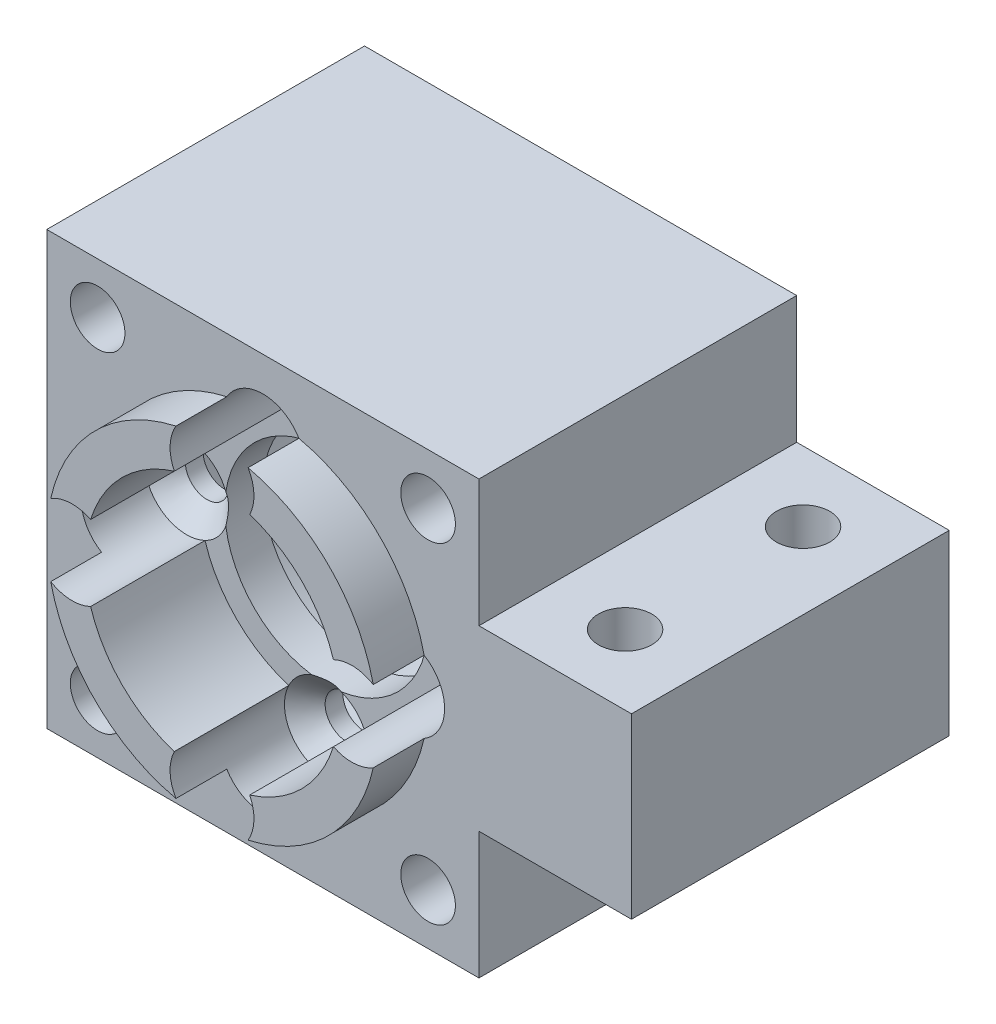
SolidWorks part; units mm, degrees
material "1060 合金"
ref_plane "前视基准面" through (0, 0, 0) normal (0, 0, 1) x (1, 0, 0)
ref_plane "上视基准面" through (0, 0, 0) normal (0, 1, 0) x (1, 0, 0)
ref_plane "右视基准面" through (0, 0, 0) normal (1, 0, 0) x (0, 0, -1)
sketch "草图1" plane through (0, 0, 0) normal (1, 0, 0) x (0, 0, -1)
  line L0 (0, 0) -> (85.2801, 0) construction
  line L1 (0, 0) -> (0, 40.8583) construction
  line L2 (0, 13) -> (0, 10)
  line L3 (0, 10) -> (9, 10)
  line L4 (9, 10) -> (9, 8)
  line L5 (9, 8) -> (12, 8)
  line L6 (12, 8) -> (12, 14)
  line L7 (12, 14) -> (29, 14)
  line L8 (29, 14) -> (29, 16)
  line L9 (29, 16) -> (4, 16)
  line L10 (0, 13) -> (4, 13)
  line L11 (4, 13) -> (4, 16)
  dimension "D1" = 8
  dimension "D2" = 3
  dimension "D3" = 13
  dimension "D4" = 14
  dimension "D5" = 2
  dimension "D6" = 17
  dimension "D7" = 4
  dimension "D8" = 8
  dimension "D9" = 10
revolve "旋转1" add sketch "草图1" angle 360 about L0
hole_wizard "打孔尺寸(%根据十字)槽沉头木螺钉的类型1" positions "草图3" profile "草图2" countersink size "M3" standard "GB" end condition through all
sketch "草图3" plane through (0, 0, 0) normal (0, 0, 1) x (1, 0, 0)
  line L0 (11, 0) -> (0, 0) construction
  line L2 (0, 0) -> (4.7674, 0) construction
  line L3 (0, 0) -> (0, 6.1766) construction
  circle A0 centre (0, 0) radius 11 construction
  point P0 (11, 0)
  point P12 (0, -11)
  point P13 (-11, 0)
  point P14 (0, 11)
  dimension "D1" = 22
  dimension "D2" = 4
sketch "草图2" plane through (11, 0, 0) normal (1, 0, 0) x (0, -1, 0)
  line L0 (0, 0) -> (0, 29)
  line L1 (0, 29) -> (1.7, 29)
  line L2 (1.7, 29) -> (1.7, 10.6)
  line L3 (1.7, 10.6) -> (3.3, 9)
  line L4 (3.3, 9) -> (3.3, 0)
  line L6 (3.3, 0) -> (0, 0)
  line L7 (-1.7, 10.6) -> (-3.3, 9) construction
  line L11 (0, -6.35) -> (0, 107.95) construction
  dimension "通孔孔直径" = 3.4
  dimension "通孔孔深度" = 29
  dimension "锥形沉头孔直径" = 6.6
  dimension "锥形沉头孔角度" = 90
  dimension "头间隙" = 9
sketch "草图4" plane through (0, 0, -4) normal (0, 0, 1) x (1, 0, 0)
  line L1 (-17, -17) -> (17, -17)
  line L2 (-17, -17) -> (-17, 17)
  line L3 (-17, 17) -> (17, 17)
  line L4 (17, -17) -> (17, 17)
  line L5 (-17, -17) -> (17, 17) construction
  line L6 (-17, 17) -> (17, -17) construction
  circle A0 centre (0, 0) radius 16
  circle A1 centre (0, 0) radius 16 construction
  point P0 (0, 0)
  dimension "D1" = 34
extrude "凸台-拉伸1" add sketch "草图4" against normal up to surface (25 mm away) up to face at (16, 0, -29)
sketch "草图11" [suppressed] plane through (0, 0, -29) normal (0, 0, -1) x (-1, 0, 0)
  line L0 (0, 0) -> (0, 25.5096) construction
  line L3 (-17, 17) -> (17, 17) construction
  line L4 (-10, 9.798) -> (10, 9.798) construction
  line L5 (-10, 9.798) -> (-10, 17)
  line L6 (-10, 17) -> (10, 17)
  line L7 (10, 9.798) -> (10, 17)
  line L8 (-10, 9.798) -> (10, 17) construction
  line L9 (-10, 17) -> (10, 9.798) construction
  circle A4 centre (0, 0) radius 14 construction
  circle A5 centre (0, 0) radius 14 construction
  arc A6 (10, 9.798) -> (-10, 9.798) centre (0, 0) ccw
  point P3 (0, 13.399)
  dimension "D1" = 20
extrude "凸台-拉伸2" [suppressed] add sketch "草图11" along normal up to surface (21 mm away) up to face at (14, 0, -29)
hole_wizard "打孔尺寸(%根据)内六角圆柱头螺钉的类型2" positions "草图10" profile "草图9" counterbore size "M4" standard "GB" end condition through all
sketch "草图10" plane through (0, 0, -29) normal (0, 0, -1) x (-1, 0, 0)
  line L0 (0, 0) -> (17, 17) construction
  line L2 (17, 17) -> (17, -17) construction
  point P0 (13, 13)
  point P26 (13, -13)
  point P27 (-13, -13)
  point P28 (-13, 13)
  dimension "D1" = 4
  dimension "D2" = 4
sketch "草图9" plane through (-13, 13, -29) normal (1, 0, 0) x (0, 1, 0)
  line L0 (0, 0) -> (0, 29)
  line L1 (0, 29) -> (2.15, 29)
  line L3 (2.15, 29) -> (2.15, 11)
  line L4 (2.15, 11) -> (3.75, 11)
  line L5 (3.75, 11) -> (3.75, 0)
  line L7 (3.75, 0) -> (0, 0)
  line L11 (0, -6.35) -> (0, 107.95) construction
  dimension "通孔孔直径" = 4.3
  dimension "通孔孔深度" = 29
  dimension "柱形沉头孔直径" = 7.5
  dimension "柱形沉头孔深度" = 11
sketch "草图12" plane through (0, -17, 0) normal (0, -1, 0) x (1, 0, 0)
  line L0 (17, -4) -> (27.3244, -14.2553)
  line L1 (27.3244, -14.2553) -> (80.5693, -51.5377)
  line L2 (17, -29) -> (17, -4)
  line L3 (17, -29) -> (27.3244, -14.2553) construction
  line L4 (80.5693, -51.5377) -> (70.2449, -66.2825)
  line L5 (70.2449, -66.2825) -> (17, -29)
  dimension "D1" = 35
  dimension "D2" = 65
  dimension "D3" = 18
extrude "凸台-拉伸3" [suppressed] add sketch "草图12" against normal up to surface (34 mm away) up to face at (0, 17, -16.5)
sketch3d "3D草图1" [suppressed]
  line L0 (0, 0, 0) -> (0, 0, 7) construction
  line L1 (0, 0, 7) -> (0, 36.7936, 7) construction
  line L2 (0, 0, 7) -> (85.6623, 0, -52.9814) construction
  line L3 (79.6572, 15.8612, -54.1479) -> (91.6674, -15.8612, -51.8149)
  line L4 (85.6623, 0, -52.9814) -> (85.6623, 15.8612, -52.9814) construction
  line L5 (85.6623, 15.8612, -52.9814) -> (82.1809, 15.8612, -50.5437) construction
  line L6 (82.1809, 15.8612, -50.5437) -> (79.6572, 15.8612, -54.1479) construction
  line L7 (82.1809, 15.8612, -50.5437) -> (85.6623, 0, -52.9814) construction
  dimension "D1" = 15
  dimension "D2" = 5
  dimension "D3" = 7
  dimension "D4" = 15
  dimension "D5" = 34
ref_axis "基准轴1" [suppressed] through (79.6572, 15.8612, -54.1479) along (0.3532, -0.933, 0.0686)
ref_point "点1" [suppressed]
sketch "草图23" [suppressed] plane through (-8.0327, 0, -11.4719) normal (-0.5736, 0, -0.8192) x (-0.8192, 0, 0.5736)
  line L0 (0, 0) -> (-89.54, 0) construction
  line L1 (4.015, 0) -> (-100.5593, 0) construction
  line L2 (-30.5593, 17) -> (-95.5593, 17) construction
  line L3 (-75.5593, -6.5) -> (-42.5593, -6.5)
  line L4 (-75.5593, -6.5) -> (-75.5593, 6.5) construction
  line L5 (-75.5593, 6.5) -> (-42.5593, 6.5)
  line L6 (-42.5593, -6.5) -> (-42.5593, 6.5) construction
  line L7 (-75.5593, -6.5) -> (-42.5593, 6.5) construction
  line L8 (-75.5593, 6.5) -> (-42.5593, -6.5) construction
  line L9 (-30.5593, 17) -> (-30.5593, -17) construction
  line L10 (-95.5593, 17) -> (-95.5593, -17) construction
  arc A0 (-75.5593, 6.5) -> (-75.5593, -6.5) centre (-75.5593, 0) ccw
  arc A1 (-42.5593, -6.5) -> (-42.5593, 6.5) centre (-42.5593, 0) ccw
  point P3 (-59.0593, 0)
  dimension "D2" = 12
  dimension "D3" = 20
  dimension "D1" = 10.5
extrude "切除-拉伸2" [suppressed] cut sketch "草图23" against normal through all
sketch "草图24" [suppressed] plane through (0, -17, 0) normal (0, -1, 0) x (1, 0, 0)
  line L0 (75.4071, -58.9101) -> (24.7393, -23.4321) construction
  line L1 (70.2449, -66.2825) -> (80.5693, -51.5377) construction
  circle A0 centre (68.8539, -54.3215) radius 4
  dimension "D1" = 8
  dimension "D2" = 8
extrude "切除-拉伸3" [suppressed] cut sketch "草图24" against normal through all
chamfer "倒角1" [suppressed] distance 6 angle 45
sketch "草图25" plane through (0, 0, 0) normal (0, 1, 0) x (1, 0, 0)
  line L1 (29, 29) -> (17, 29)
  line L2 (29, 29) -> (29, 4)
  line L3 (29, 4) -> (17, 4)
  line L4 (17, 29) -> (17, 4)
  line L5 (29, 29) -> (17, 4) construction
  line L6 (29, 4) -> (17, 29) construction
  point P0 (23, 16.5)
  dimension "D1" = 12
extrude "凸台-拉伸4" add sketch "草图25" along normal mid plane 14
hole_wizard "M5 螺纹孔1" positions "草图27" profile "草图26" tap size "M5" standard "GB" end condition up to next
sketch "草图27" plane through (0, 7, 0) normal (0, 1, 0) x (1, 0, 0)
  line L0 (29, 16.5) -> (17, 16.5) construction
  line L1 (29, 4) -> (29, 29) construction
  line L2 (17, 29) -> (17, 4) construction
  line L4 (23, 16.5) -> (23, 31.8734) construction
  point P0 (23, 23.5)
  point P2 (23, 9.5)
  dimension "D1" = 14
sketch "草图26" plane through (23, 7, -23.5) normal (1, 0, 0) x (0, 0, 1)
  line L0 (0, 0) -> (0, 14)
  line L1 (0, 14) -> (2.1, 14)
  line L2 (2.1, 14) -> (2.1, 0)
  line L5 (2.1, 0) -> (0, 0)
  line L11 (0, -6.35) -> (0, 107.95) construction
  dimension "螺纹线主直径" = 4.2
  dimension "通孔螺纹孔钻头深度" = 14
move or copy body "实体-移动/复制2" [suppressed] bodies to move or copy 138
move or copy body "实体-移动/复制1" [suppressed] bodies to move or copy 124
